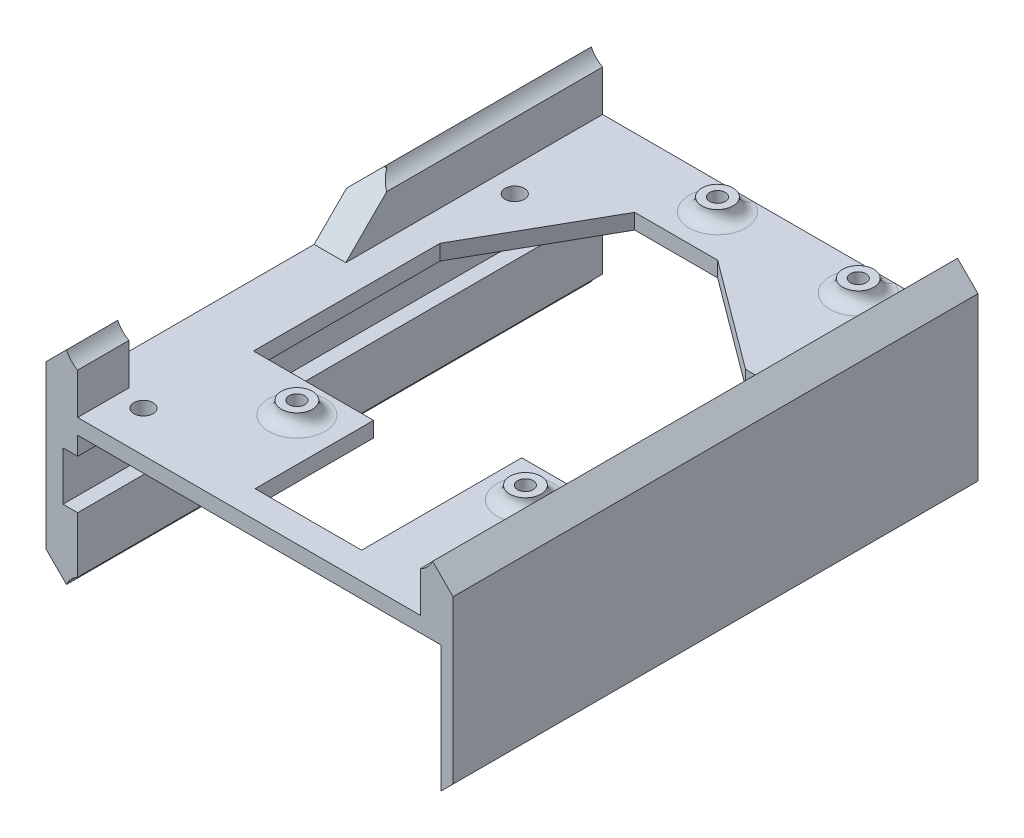
SolidWorks part; units mm, degrees
ref_plane "Front Plane" through (0, 0, 0) normal (0, 0, 1) x (1, 0, 0)
ref_plane "Top Plane" through (0, 0, 0) normal (0, 1, 0) x (1, 0, 0)
ref_plane "Right Plane" through (0, 0, 0) normal (1, 0, 0) x (0, 0, -1)
sketch "Sketch1" plane through (0, 0, 0) normal (0, 0, 1) x (1, 0, 0)
  line L0 (30.5748, -38.6095) -> (73.1149, -38.6095)
  line L1 (80.4449, -35.6839) -> (83.6448, -32.484)
  line L2 (83.6448, -32.484) -> (83.6448, -7.1349)
  line L3 (83.6448, -7.1349) -> (80.4449, -3.935)
  line L4 (73.1149, -1.0095) -> (30.5748, -1.0095)
  line L5 (23.2448, -3.935) -> (20.0448, -7.1349)
  line L6 (20.0448, -7.1349) -> (20.0448, -32.484)
  line L7 (20.0448, -32.484) -> (23.2448, -35.6839)
  line L8 (30.2818, -38.8095) -> (73.4079, -38.8095)
  line L9 (19.8448, -32.5668) -> (23.3167, -36.0387)
  line L10 (19.8448, -7.0521) -> (19.8448, -32.5668)
  line L11 (23.3167, -3.5802) -> (19.8448, -7.0521)
  line L12 (73.4079, -0.8095) -> (30.2818, -0.8095)
  line L13 (83.8448, -7.0521) -> (80.3729, -3.5802)
  line L14 (83.8448, -32.5668) -> (83.8448, -7.0521)
  line L15 (80.3729, -36.0387) -> (83.8448, -32.5668)
  line L16 (30.2818, -38.8095) -> (73.4079, -38.8095)
  line L17 (19.8448, -32.5668) -> (23.3167, -36.0387)
  line L18 (19.8448, -7.0521) -> (19.8448, -32.5668)
  line L19 (23.3167, -3.5802) -> (19.8448, -7.0521)
  line L20 (73.4079, -0.8095) -> (30.2818, -0.8095)
  line L21 (83.8448, -7.0521) -> (80.3729, -3.5802)
  line L22 (83.8448, -32.5668) -> (83.8448, -7.0521)
  line L23 (80.3729, -36.0387) -> (83.8448, -32.5668)
  arc A0 (80.4449, -35.6839) -> (73.1149, -38.6095) centre (76.8448, -37.3095) ccw
  arc A1 (73.1149, -1.0095) -> (80.4449, -3.935) centre (76.8448, -2.3095) ccw
  arc A3 (23.2448, -3.935) -> (30.5748, -1.0095) centre (26.8448, -2.3095) ccw
  arc A4 (80.3729, -36.0387) -> (73.4079, -38.8095) centre (76.8448, -37.3095) ccw
  arc A5 (30.2818, -38.8095) -> (23.3167, -36.0387) centre (26.8448, -37.3095) ccw
  arc A6 (23.3167, -3.5802) -> (30.2818, -0.8095) centre (26.8448, -2.3095) ccw
  arc A7 (73.4079, -0.8095) -> (80.3729, -3.5802) centre (76.8448, -2.3095) ccw
  arc A8 (80.3729, -36.0387) -> (73.4079, -38.8095) centre (76.8448, -37.3095) ccw
  arc A9 (30.2818, -38.8095) -> (23.3167, -36.0387) centre (26.8448, -37.3095) ccw
  arc A10 (23.3167, -3.5802) -> (30.2818, -0.8095) centre (26.8448, -2.3095) ccw
  arc A11 (73.4079, -0.8095) -> (80.3729, -3.5802) centre (76.8448, -2.3095) ccw
  arc A13 (30.5748, -38.6095) -> (23.2448, -35.6839) centre (26.8448, -37.3095) ccw
  dimension "D1" = 0
  dimension "D2" = 0.2
extrude "Boss-Extrude1" add sketch "Sketch1" against normal blind 82 contours A13 L0 A0 L1 L2 L3 A1 L4 A3 L5 L6 L7 region at (51.8448, -19.8095, 0)
sketch "Sketch2" plane through (0, -38.6095, 0) normal (0, -1, 0) x (1, 0, 0)
  line L1 (24.9892, -88.1764) -> (81.731, -88.1764)
  line L2 (24.9892, -88.1764) -> (24.9892, 2.0928)
  line L3 (24.9892, 2.0928) -> (81.731, 2.0928)
  line L4 (81.731, -88.1764) -> (81.731, 2.0928)
extrude "Cut-Extrude1" cut sketch "Sketch2" against normal blind 24
sketch "Sketch3" plane through (0, -1.0095, 0) normal (0, 1, 0) x (1, 0, 0)
  line L1 (24.9892, 82) -> (78.5389, 82)
  line L2 (24.9892, 82) -> (24.9892, -3.0245)
  line L3 (24.9892, -3.0245) -> (78.5389, -3.0245)
  line L4 (78.5389, 82) -> (78.5389, -3.0245)
extrude "Cut-Extrude2" cut sketch "Sketch3" against normal blind 11.2
sketch "Sketch7" plane through (0, -12.2095, 0) normal (0, 1, 0) x (1, 0, 0)
  line L1 (42.3691, 49.8866) -> (18.7852, 49.8866)
  line L2 (42.3691, 49.8866) -> (42.3691, 8.0085)
  line L3 (42.3691, 8.0085) -> (18.7852, 8.0085)
  line L4 (18.7852, 49.8866) -> (18.7852, 8.0085)
extrude "Cut-Extrude6" cut sketch "Sketch7" along normal through all
sketch "Sketch9" plane through (0, -12.2095, 0) normal (0, 1, 0) x (1, 0, 0)
  circle A0 centre (47.1229, 77.8184) radius 1.225
  circle A1 centre (69.1229, 77.8184) radius 1.225
  circle A2 centre (71.1229, 23.8184) radius 1.225
  circle A3 centre (24.2805, 35.2503) radius 1.225
  circle A4 centre (41.7805, 17.4607) radius 1.225
  dimension "D1" = 2.45
extrude "Extrude-Thin1" add sketch "Sketch9" along normal blind 2 thin contours A4 | A2 | A0 | A1 thin type one direction wall 1.2
sketch "Sketch10" plane through (0, -14.6095, 0) normal (0, -1, 0) x (1, 0, 0)
  circle A0 centre (28.8717, -6.4) radius 1.5
  circle A1 centre (77.8717, -6.4) radius 1.5
  circle A2 centre (77.8717, -64.4) radius 1.5
  circle A3 centre (28.8717, -64.4) radius 1.5
  dimension "D1" = 3
extrude "Extrude-Thin2" add sketch "Sketch10" along normal blind 2 thin thin type one direction wall 1.2
fillet "Fillet1" radius 2 8 edges at (73.5479, -12.2095, -23.8184) (44.2055, -12.2095, -17.4607) (49.5479, -12.2095, -77.8184) (71.5479, -12.2095, -77.8184) (77.8717, -14.6095, -3.7) (77.8717, -14.6095, -61.7) (28.8717, -14.6095, -3.7) (28.8717, -14.6095, -61.7)
sketch "Sketch12" plane through (0, 0, 0) normal (0, 0, 1) x (1, 0, 0)
  line L0 (25.1967, -31.6479) -> (25.1967, -16.6479) construction
  line L1 (24.9892, -25.0909) -> (22.6967, -25.0909)
  line L2 (24.9892, -25.0909) -> (24.9892, -17.4623)
  line L3 (24.9892, -17.4623) -> (22.6967, -17.4623)
  line L4 (22.6967, -25.0909) -> (22.6967, -17.4623)
  line L5 (24.9892, -14.6095) -> (24.9892, -33.8225) construction
  dimension "D1" = 2.5
extrude "Cut-Extrude7" cut sketch "Sketch12" against normal through all
sketch "Sketch13" plane through (0, -14.6095, 0) normal (0, -1, 0) x (1, 0, 0)
  circle A0 centre (77.8717, -6.4) radius 1.5 construction
  circle A1 centre (77.8717, -64.4) radius 1.5 construction
  circle A2 centre (28.8717, -64.4) radius 1.5 construction
  circle A3 centre (28.8717, -6.4) radius 1.5 construction
  circle A4 centre (77.8717, -6.4) radius 1.5
  circle A5 centre (77.8717, -64.4) radius 1.5
  circle A6 centre (28.8717, -64.4) radius 1.5
  circle A7 centre (28.8717, -6.4) radius 1.5
extrude "Cut-Extrude8" cut sketch "Sketch13" against normal through all
sketch "Sketch14" plane through (0, -12.2095, 0) normal (0, 1, 0) x (1, 0, 0)
  circle A0 centre (69.1229, 77.8184) radius 1.225 construction
  circle A1 centre (71.1229, 23.8184) radius 1.225 construction
  circle A2 centre (41.7805, 17.4607) radius 1.225 construction
  circle A4 centre (47.1229, 77.8184) radius 1.225 construction
  circle A5 centre (69.1229, 77.8184) radius 1.225
  circle A6 centre (71.1229, 23.8184) radius 1.225
  circle A7 centre (41.7805, 17.4607) radius 1.225
  circle A9 centre (47.1229, 77.8184) radius 1.225
extrude "Cut-Extrude9" cut sketch "Sketch14" against normal through all
chamfer "Chamfer1" distance 8 angle 45 1 edges at (22.517, -12.2095, -49.8866)
sketch "Sketch15" plane through (0, -12.2095, 0) normal (0, 1, 0) x (1, 0, 0)
  line L0 (29.7332, 51.8741) -> (29.7332, 22.7246)
  line L1 (29.7332, 22.7246) -> (48.4902, 22.7246)
  line L3 (65.1264, 29.2394) -> (76.9119, 29.2394)
  line L4 (76.9119, 29.2394) -> (76.9119, 58.6828)
  line L5 (76.9119, 58.6828) -> (70.6468, 58.6828)
  line L6 (70.6468, 58.6828) -> (53.7063, 71.2685)
  line L7 (53.7063, 71.2685) -> (40.7487, 71.2685)
  line L8 (40.7487, 71.2685) -> (29.7332, 51.8741)
  line L9 (48.4902, 22.7246) -> (48.4902, 4.225)
  line L10 (48.4902, 4.225) -> (65.1264, 4.225)
  line L12 (65.1264, 29.2394) -> (65.1264, 4.225)
extrude "Cut-Extrude10" cut sketch "Sketch15" against normal through all
